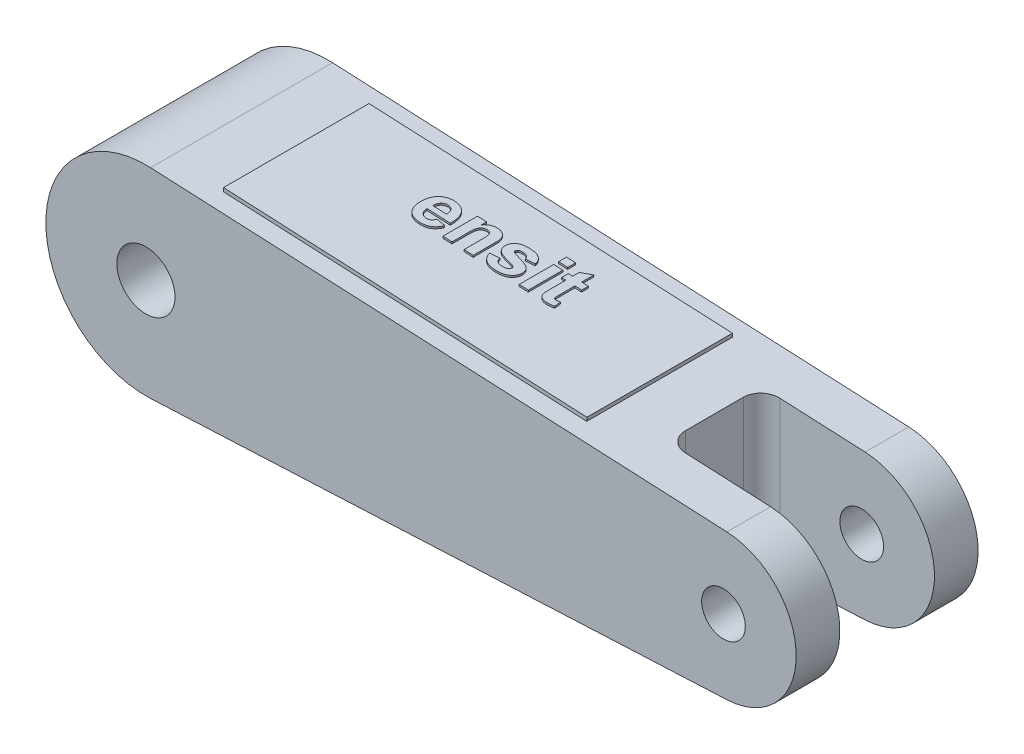
SolidWorks part; units mm, degrees
material "Alliage 6061"
ref_plane "Plan de face" through (0, 0, 0) normal (0, 0, 1) x (1, 0, 0)
ref_plane "Plan de dessus" through (0, 0, 0) normal (0, 1, 0) x (1, 0, 0)
ref_plane "Plan de droite" through (0, 0, 0) normal (1, 0, 0) x (0, 0, -1)
sketch "Esquisse1" plane through (0, 0, 0) normal (0, 0, 1) x (1, 0, 0)
  line L0 (0, 0) -> (317.5, 0) construction
  line L1 (2.5984, -54.9386) -> (319.3898, -39.9553)
  line L2 (319.3898, 39.9553) -> (2.5984, 54.9386)
  arc A0 (2.5984, 54.9386) -> (2.5984, -54.9386) centre (0, 0) ccw
  arc A1 (319.3898, -39.9553) -> (319.3898, 39.9553) centre (317.5, 0) ccw
  dimension "D2" = 55
  dimension "D3" = 40
  dimension "D1" = 317.5
extrude "Boss.-Extru.1" add sketch "Esquisse1" against normal blind 100
sketch "Esquisse2" plane through (0, 0, 0) normal (0, 0, 1) x (1, 0, 0)
  line L0 (0, 0) -> (317.5, 0) construction
  circle A0 centre (0, 0) radius 16
  circle A1 centre (317.5, 0) radius 12
  dimension "D2" = 32
  dimension "D3" = 24
  dimension "D1" = 317.5
extrude "Enlèv. mat.-Extru.1" cut sketch "Esquisse2" against normal through all
sketch "Esquisse3" plane through (0, 0, 0) normal (0, 1, 0) x (1, 0, 0)
  line L0 (0, 0) -> (0, 50) construction
  line L1 (0, 50) -> (370, 50) construction
  line L2 (262.5, 66) -> (262.5, 34)
  line L3 (272.5, 24) -> (370, 24)
  line L4 (370, 24) -> (370, 76)
  line L5 (370, 76) -> (272.5, 76)
  arc A0 (262.5, 66) -> (272.5, 76) centre (272.5, 66) cw
  arc A1 (262.5, 34) -> (272.5, 24) centre (272.5, 34) ccw
  dimension "D5" = 10
  dimension "D6" = 10
  dimension "D1" = 50
  dimension "D2" = 370
  dimension "D3" = 262.5
  dimension "D4" = 52
extrude "Enlèv. mat.-Extru.2" cut sketch "Esquisse3" against normal through all and the other way through all
sketch "Esquisse4" plane through (2.5984, 54.9386, 0) normal (0.0472, 0.9989, 0) x (0.9989, -0.0472, 0)
  line L0 (0, 50) -> (230, 50) construction
  line L1 (30, 90) -> (30, 10)
  line L2 (30, 10) -> (230, 10)
  line L3 (230, 10) -> (230, 90)
  line L4 (230, 90) -> (30, 90)
  line L5 (0, 100) -> (0, 0) construction
  line L6 (317.1455, 0) -> (0, 0) construction
  dimension "D1" = 10
  dimension "D2" = 30
  dimension "D3" = 200
extrude "Boss.-Extru.2" add sketch "Esquisse4" along normal blind 2
sketch "Esquisse5" plane through (2.6929, 56.9364, 0) normal (0.0472, 0.9989, 0) x (0.9989, -0.0472, 0)
  line L0 (30, 50) -> (230, 50) construction
  line L1 (30, 90) -> (30, 10) construction
  line L2 (230, 10) -> (230, 90) construction
  text T0 "ensit" font "Arial" height 26
extrude "Boss.-Extru.3" add sketch "Esquisse5" along normal blind 1
ref_axis "Axis_J3" through (0, 0, -100) along (0, 0, 1)
ref_axis "Axis_J4" through (317.5, 0, -100) along (0, 0, 1)
